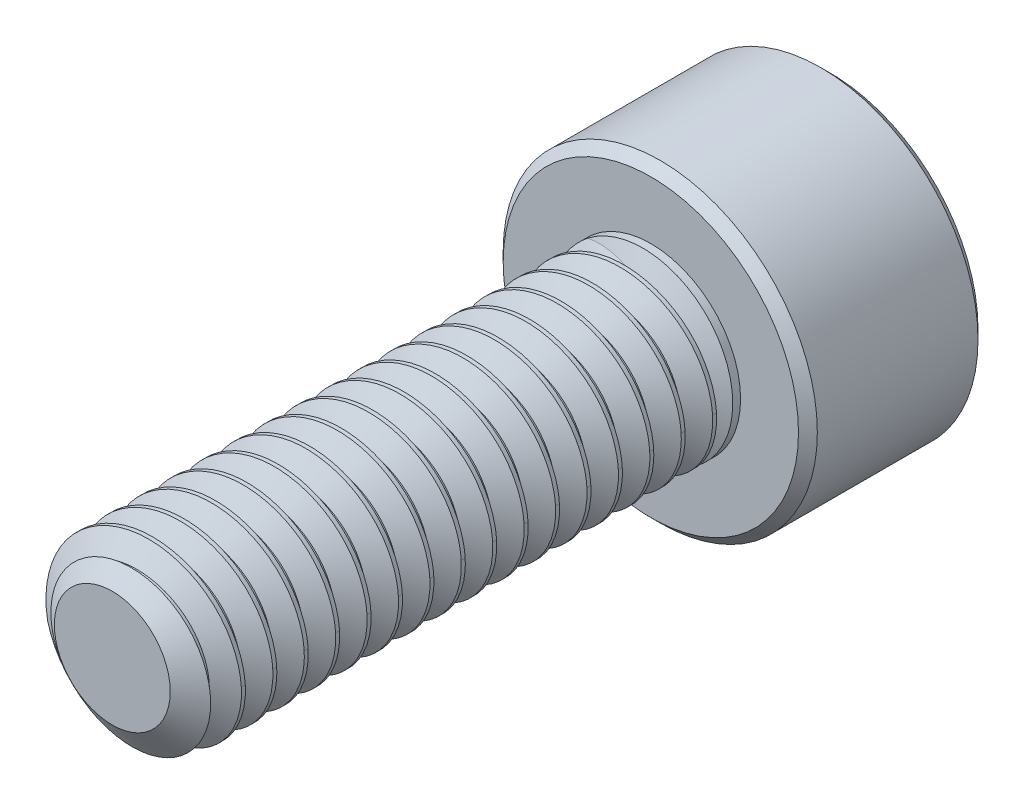
SolidWorks part; units mm, degrees
material "Plain Carbon Steel"
ref_plane "Front Plane" through (0, 0, 0) normal (0, 0, 1) x (1, 0, 0)
ref_plane "Top Plane" through (0, 0, 0) normal (0, 1, 0) x (1, 0, 0)
ref_plane "Right Plane" through (0, 0, 0) normal (1, 0, 0) x (0, 0, -1)
sketch "Sketch1" plane through (0, 0, 0) normal (0, 0, 1) x (1, 0, 0)
  circle A0 centre (0, 0) radius 2
  dimension "OD" = 4
extrude "Extrude1" add sketch "Sketch1" against normal blind 12
sketch "Sketch2" plane through (0, 0, 0) normal (0, 0, 1) x (1, 0, 0)
  circle A0 centre (0, 0) radius 2 construction
  circle A1 centre (0, 0) radius 2
curve "Helix/Spiral1" pitch 0.7 height 12.7 radius 2 centre (0, 0, 0) axis (0, 0, -1) start towards (0, 1, 0) parameters "pitch"=0.7
sketch "Sketch3" plane through (0, 0, 0) normal (1, 0, 0) x (0, 0, -1)
  line L0 (-0.6125, 2) -> (-0.35, 1.5453)
  line L1 (-0.35, 1.5453) -> (-0.2625, 1.5453)
  line L2 (-0.2625, 1.5453) -> (0, 2)
  line L3 (-0.6125, 2) -> (0, 2)
  line L4 (-0.3063, 2) -> (-0.3063, 1.5453) construction
  line L5 (-0.4813, 1.7727) -> (-0.1313, 1.7727) construction
  line L6 (0, 2) -> (0, -2) construction
  line L7 (0, -2) -> (12, -2) construction
  point P11 (3.15, -2)
  dimension "D1" = 0.0875
  dimension "D2" = 0.35
  dimension "D3" = 60
  dimension "D4" = 3.15
sweep "Cut-Sweep1" cut profiles "Sketch3" path "Helix/Spiral1"
sketch "Sketch4" plane through (0, 0, 0) normal (1, 0, 0) x (0, 0, -1)
  line L0 (0.4962, 2) -> (0, 1.2913)
  line L1 (0, 1.2913) -> (0, 2)
  line L2 (0.4962, 2) -> (0, 2)
  line L3 (-0.6125, 2) -> (0, 2) construction
  line L4 (0, 0) -> (7.0209, 0) construction
  dimension "D1" = 55
  dimension "D2" = 0.254
revolve "Cut-Revolve1" cut sketch "Sketch4" angle 360 about L4
sketch "Sketch5" plane through (0, 0, 0) normal (1, 0, 0) x (0, 0, -1)
  line L0 (12, -0.9741) -> (12, 1.9864) construction
  line L1 (12, 2) -> (0.1203, 2)
  line L2 (12, 2) -> (12, 0)
  line L3 (12, 0) -> (0.0001, 0)
  line L4 (0.0001, 1.6698) -> (0.0001, 0)
  line L5 (0.1203, 2) -> (0.0001, 1.6698)
  line L6 (0, 0) -> (9.9695, 0) construction
  point P3 (0.0001, 2)
  point P10 (0.0001, 2)
  dimension "D1" = 0.3302
  dimension "Thread min" = 0.0001
  dimension "D3" = 20
revolve "partially thread" [suppressed] add sketch "Sketch5" angle 360 about L6
sketch "Sketch6" plane through (0, 0, -12) normal (0, 0, -1) x (-1, 0, 0)
  circle A0 centre (0, 0) radius 3.5
  dimension "head dia" = 7
extrude "Extrude2" add sketch "Sketch6" along normal blind 4
sketch "Sketch7" plane through (0, 0, -16) normal (0, 0, -1) x (-1, 0, 0)
  line L1 (0, 1.7321) -> (-1.5, 0.866)
  line L2 (-1.5, 0.866) -> (-1.5, -0.866)
  line L3 (-1.5, -0.866) -> (0, -1.7321)
  line L4 (0, -1.7321) -> (1.5, -0.866)
  line L5 (1.5, -0.866) -> (1.5, 0.866)
  line L6 (1.5, 0.866) -> (0, 1.7321)
  circle A0 centre (0, 0) radius 1.5 construction
  dimension "hex dia" = 3
extrude "Cut-Extrude1" cut sketch "Sketch7" against normal blind 2.25
sketch "Sketch8" plane through (0, 0, -16) normal (0, 0, -1) x (-1, 0, 0)
  circle A0 centre (0, 0) radius 1.7321
extrude "Cut-Extrude2" cut sketch "Sketch8" against normal through all draft 45
chamfer "Chamfer1" distance 0.21 angle 45 2 edges at (-3.5, 0, -16) (-3.5, 0, -12)
sketch "Sketch9" plane through (0, 0, 0) normal (1, 0, 0) x (0, 0, -1)
  line L0 (0, 2) -> (0, -2) construction
  line L1 (3.85, 2) -> (3.85, -2) construction
  dimension "D1" = 3.85
sketch "Sketch10" plane through (0, 0, 0) normal (1, 0, 0) x (0, 0, -1)
  line L0 (12, 2) -> (12, 0)
  line L1 (12, 2) -> (11.825, 2)
  line L2 (11.825, 2) -> (10.9966, 0)
  line L3 (12, 0) -> (10.9966, 0)
  line L4 (12, 3.29) -> (12, -3.29) construction
  dimension "D1" = 22.5
  dimension "D2" = 0.175
revolve "Revolve1" add sketch "Sketch10" angle 360 about L3
equation "\"D3@Helix/Spiral1\" = \"screw length@Extrude1\"+\"pitch@Helix/Spiral1\""
equation "\"D1@Sketch3\" = \"pitch@Helix/Spiral1\"*.125"
equation "\"D2@Sketch3\" = \"pitch@Helix/Spiral1\"*.5"
equation "\"D1@Cut-Extrude1\" = \"hex dia@Sketch7\"*.75"
equation "\"D1@Chamfer1\" = \"head dia@Sketch6\"*.03"
equation "\"D1@Sketch9\" = \"pitch@Helix/Spiral1\"*5.5"
equation "\"D2@Sketch10\" = \"pitch@Helix/Spiral1\"*.25"
equation "\"D4@Sketch3\" = \"pitch@Helix/Spiral1\"*4.50"
